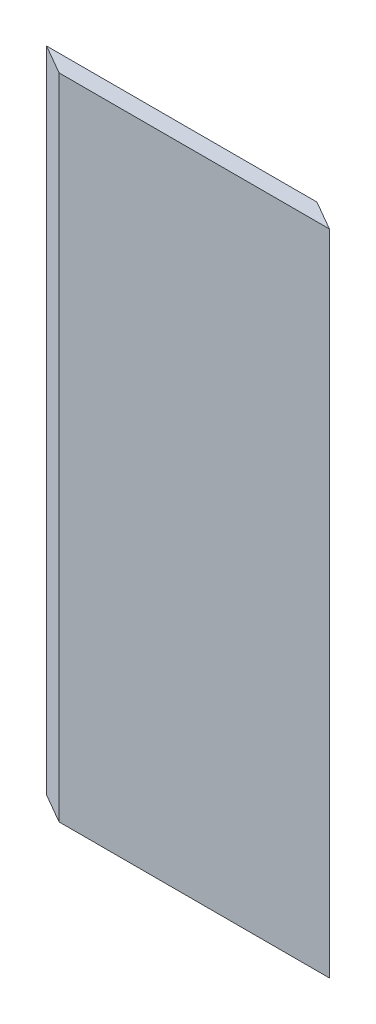
SolidWorks part; units mm, degrees
ref_plane "Front Plane" through (0, 0, 0) normal (0, 0, 1) x (1, 0, 0)
ref_plane "Top Plane" through (0, 0, 0) normal (0, 1, 0) x (1, 0, 0)
ref_plane "Right Plane" through (0, 0, 0) normal (1, 0, 0) x (0, 0, -1)
sketch "Sketch1" plane through (0, 0, 0) normal (0, 0, 1) x (1, 0, 0)
  line L0 (53.7926, 0) -> (53.7926, -121.92)
  line L1 (53.7926, -121.92) -> (2.9926, -121.92)
  line L2 (2.9926, -121.92) -> (2.9926, 0)
  line L3 (2.9926, 0) -> (53.7926, 0)
extrude "Boss-Extrude1" add sketch "Sketch1" against normal blind 3.2
sketch "Sketch2" plane through (0, -121.92, 0) normal (0, -1, 0) x (1, 0, 0)
  line L0 (53.7926, 0) -> (53.7926, -3.2)
  line L1 (53.7926, -3.2) -> (48.2501, -3.2)
  line L2 (2.9926, -3.2) -> (53.7926, -3.2) construction
  line L3 (-56.1926, -63.5) -> (53.7926, 0) construction
  line L4 (48.2501, -3.2) -> (53.7926, 0)
extrude "Cut-Extrude1" cut sketch "Sketch2" against normal through all
sketch "Sketch4" plane through (0, -121.92, 0) normal (0, -1, 0) x (1, 0, 0)
  line L0 (2.9926, 0) -> (2.9926, -3.2)
  line L1 (2.9926, -3.2) -> (-2.5499, -3.2)
  line L3 (-2.5499, -3.2) -> (2.9926, 0)
extrude "Boss-Extrude2" add sketch "Sketch4" against normal up to surface (121.92 mm away) up to face at (27.007, 0, -1.6)
